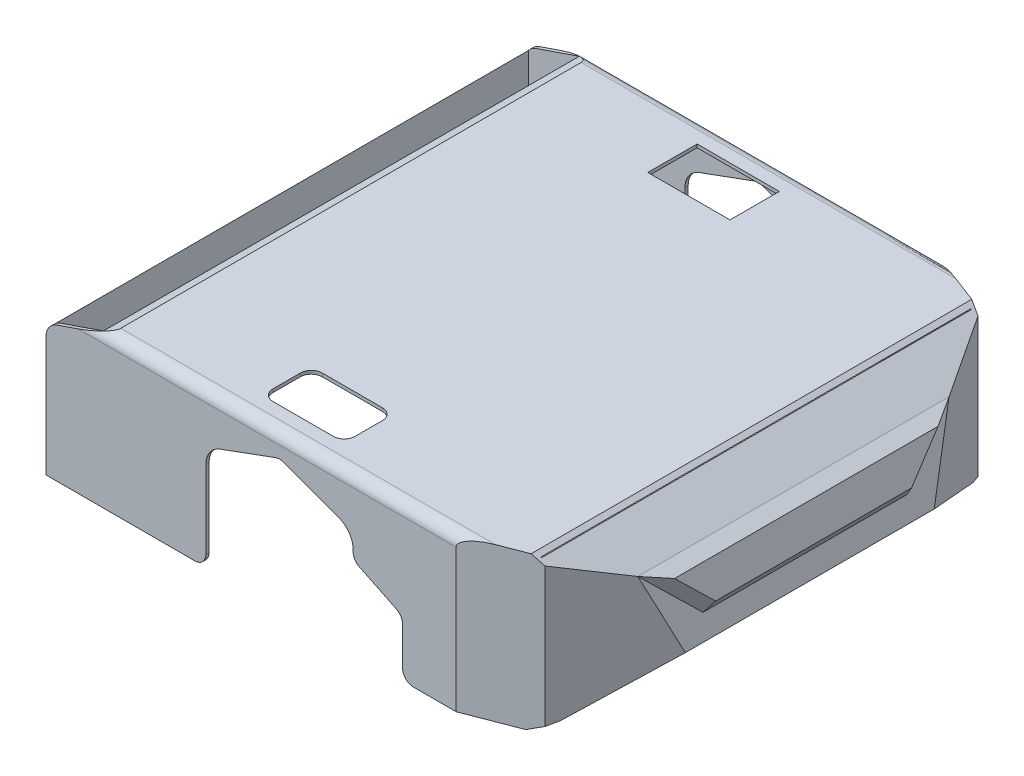
SolidWorks part; units mm, degrees
material "CA"
ref_plane "Front Plane" through (0, 0, 0) normal (0, 0, 1) x (1, 0, 0)
ref_plane "Top Plane" through (0, 0, 0) normal (0, 1, 0) x (1, 0, 0)
ref_plane "Right Plane" through (0, 0, 0) normal (1, 0, 0) x (0, 0, -1)
sketch "Sketch1" plane through (0, 0, 0) normal (0, 0, 1) x (1, 0, 0)
  line L1 (0, 0) -> (480, 0)
  line L2 (0, 0) -> (0, 140)
  line L3 (0, 140) -> (480, 140)
  line L4 (480, 0) -> (480, 140)
  dimension "D1" = 480
  dimension "D2" = 140
extrude "Boss-Extrude1" add sketch "Sketch1" along normal blind 440
sketch "Sketch2" plane through (0, 0, 440) normal (0, 0, 1) x (1, 0, 0)
  line L1 (0, 0) -> (420, 0)
  line L2 (0, 0) -> (0, 120)
  line L3 (0, 120) -> (420, 120)
  line L4 (420, 0) -> (420, 120)
  dimension "D1" = 120
  dimension "D2" = 420
sketch "Sketch3" plane through (0, 0, 440) normal (0, 0, 1) x (1, 0, 0)
  line L0 (0, 120) -> (58.2254, 140)
  line L1 (480, 140) -> (0, 140) construction
  line L2 (58.2254, 140) -> (423.4831, 140)
  line L3 (423.4831, 140) -> (461.8504, 111.6906)
  line L4 (461.8504, 111.6906) -> (480, 30.0603)
  line L5 (480, 0) -> (480, 140) construction
  line L6 (480, 30.0603) -> (420, 0)
  line L7 (0, 120) -> (0, 186.0028)
  line L8 (0, 186.0028) -> (591.5196, 186.0028)
  line L9 (591.5196, 186.0028) -> (591.5196, 0)
  line L10 (591.5196, 0) -> (420, 0)
  line L11 (480, 140) -> (0, 140) construction
extrude "Cut-Extrude2" cut sketch "Sketch3" against normal through all
chamfer "Chamfer1" distance 15 angle 60 1 edges at (480, 30.0603, 220) first distance on face at (470.9252, 70.8754, 220)
sketch "Sketch4" plane through (0, 140, 0) normal (0, 1, 0) x (1, 0, 0)
  line L2 (476.7444, -333.5325) -> (476.7444, -106.4675)
  line L5 (374.147, -440) -> (432.7602, -417.4465)
  line L7 (432.7602, -417.4465) -> (476.7444, -333.5325)
  line L8 (476.7444, -333.5325) -> (476.7444, -220)
  line L9 (476.7444, -440) -> (476.7444, 0) construction
  line L10 (476.7444, -333.5325) -> (476.7444, -220)
  line L11 (476.7444, -220) -> (259.9754, -220) construction
  line L13 (374.147, -440) -> (571.4453, -440)
  line L14 (571.4453, -440) -> (571.4453, 0)
  line L15 (571.4453, 0) -> (374.147, 0)
  line L16 (374.147, 0) -> (432.7602, -22.5535)
  line L17 (432.7602, -22.5535) -> (476.7444, -106.4675)
  line L18 (423.4831, 0) -> (58.2254, 0) construction
  point P14 (476.7444, -220)
extrude "Cut-Extrude3" cut sketch "Sketch4" against normal blind 335 contours L2 L17 L16 L15 L14 L13 L5 L7
fillet "Fillet1" radius 10 2 edges at (216.1862, 140, 0) (216.1862, 140, 440)
fillet "Fillet2" radius 15 1 edges at (0, 120, 220)
sketch "Sketch6" plane through (463.7578, 103.1116, 0) normal (0.9762, 0.217, 0) x (0, 0, -1)
  line L0 (-361.9476, 8.7884) -> (-313.0975, -39.8352)
  line L1 (-313.0975, -39.8352) -> (-126.9025, -39.8352)
  line L2 (-361.9476, 8.7884) -> (-78.0524, 8.7884)
  line L3 (-333.5325, -59.8352) -> (-106.4675, -59.8352)
  line L4 (-220, -59.8352) -> (-220, -40.6647) construction
  line L5 (-78.0524, 8.7884) -> (-361.9476, 8.7884) construction
  line L6 (-78.0524, 8.7884) -> (-126.9025, -39.8352)
  point P10 (-220, -39.8352)
  point P15 (-220, 8.7884)
  line M9 (-78.0524, 8.7884) -> (-361.9476, 8.7884)
  dimension "D1" = 20
extrude "Boss-Extrude2" add sketch "Sketch6" along direction (-0.9762, -0.217, 0) on the side of the normal blind 10 draft 42 contours L4 L1 L6 M9 | L1 L4 L2 L0 region at (466.7614, 89.6024, 220)
sketch "Sketch7" plane through (0, 0, 0) normal (0, -1, 0) x (1, 0, 0)
  line L1 (428.0503, 416.0444) -> (373.5897, 437)
  line L2 (373.5897, 437) -> (3, 437)
  line L3 (3, 437) -> (3, 3)
  line L4 (3, 3) -> (373.5897, 3)
  line L5 (373.5897, 3) -> (428.0503, 23.9556)
  line L14 (428.0503, 23.9556) -> (428.0503, 416.0444)
extrude "Cut-Extrude4" cut sketch "Sketch7" against normal offset from surface (137 mm away) 3 contours L1 L2 L3 L4 L5 L14 up to face at (293.948, 140, 220)
sketch "Sketch8" plane through (0, 140, 0) normal (0, 1, 0) x (1, 0, 0)
  line L0 (58.2254, -220) -> (508.1789, -220) construction
  line L1 (58.2254, -10) -> (58.2254, -430) construction
  line L2 (213, -58.5371) -> (213, -29.5371) construction
  line L3 (200.5, -44.0371) -> (229.5, -44.0371) construction
  line L5 (229.5, -34.5371) -> (229.5, -53.5371) construction
  line L6 (185.5, -373.4629) -> (240.5, -373.4629)
  line L7 (175.5, -66.5371) -> (250.5, -66.5371)
  line L8 (175.5, -66.5371) -> (175.5, -21.5371)
  line L9 (175.5, -21.5371) -> (250.5, -21.5371)
  line L10 (250.5, -66.5371) -> (250.5, -21.5371)
  line L11 (175.5, -66.5371) -> (250.5, -21.5371) construction
  line L12 (175.5, -21.5371) -> (250.5, -66.5371) construction
  line L13 (175.5, -383.4629) -> (175.5, -408.4629)
  line L14 (185.5, -418.4629) -> (240.5, -418.4629)
  line L15 (250.5, -383.4629) -> (250.5, -408.4629)
  arc A0 (185.5, -373.4629) -> (175.5, -383.4629) centre (185.5, -383.4629) ccw
  arc A1 (240.5, -373.4629) -> (250.5, -383.4629) centre (240.5, -383.4629) cw
  arc A2 (175.5, -408.4629) -> (185.5, -418.4629) centre (185.5, -408.4629) ccw
  arc A3 (240.5, -418.4629) -> (250.5, -408.4629) centre (240.5, -408.4629) ccw
  point P17 (213, -44.0371)
  point P25 (175.5, -373.4629)
  point P28 (250.5, -373.4629)
  point P31 (175.5, -418.4629)
  point P34 (250.5, -418.4629)
  dimension "D3" = 10
  dimension "D1" = 75
  dimension "D2" = 45
extrude "Cut-Extrude5" cut sketch "Sketch8" against normal blind 10
sketch "Sketch9" plane through (0, 0, 440) normal (0, 0, 1) x (1, 0, 0)
  line L0 (213, 48.5752) -> (213, 127) construction
  line L1 (213, 119.686) -> (158.9171, 99.8501)
  line L2 (145.8038, 81.0732) -> (145.8038, 0)
  line L3 (0, 0) -> (374.147, 0) construction
  line L4 (145.8038, 0) -> (280.1962, 0)
  line L5 (280.1962, 81.0732) -> (280.1962, 0)
  line L6 (213, 119.686) -> (267.0829, 99.8501)
  arc A1 (158.9171, 99.8501) -> (145.8038, 81.0732) centre (165.8038, 81.0732) ccw
  arc A2 (267.0829, 99.8501) -> (280.1962, 81.0732) centre (260.1962, 81.0732) cw
  point P15 (213, 0)
  dimension "D1" = 20
extrude "Cut-Extrude6" cut sketch "Sketch9" against normal blind 674
sketch "Sketch10" plane through (0, 0, 440) normal (0, 0, 1) x (1, 0, 0)
  line L0 (280.1962, 73.1231) -> (319.6001, 53.8513)
  line L1 (280.1962, 0) -> (280.1962, 81.0732) construction
  line L2 (325.2066, 44.8682) -> (325.2066, 0)
  line L3 (280.1962, 0) -> (374.147, 0) construction
  line L4 (325.2066, 0) -> (280.1962, 0)
  line L5 (280.1962, 0) -> (280.1962, 73.1231)
  arc A0 (319.6001, 53.8513) -> (325.2066, 44.8682) centre (315.2066, 44.8682) cw
  dimension "D1" = 10
extrude "Cut-Extrude7" cut sketch "Sketch10" against normal through all
fillet "Fillet3" radius 10 8 edges at (325.2066, 0, 1.5) (145.8038, 0, 1.5) (280.1962, 73.1231, 1.5) (213, 119.686, 1.5) (325.2066, 0, 438.5) (280.1962, 73.1231, 438.5) (145.8038, 0, 438.5) (213, 119.686, 438.5)
